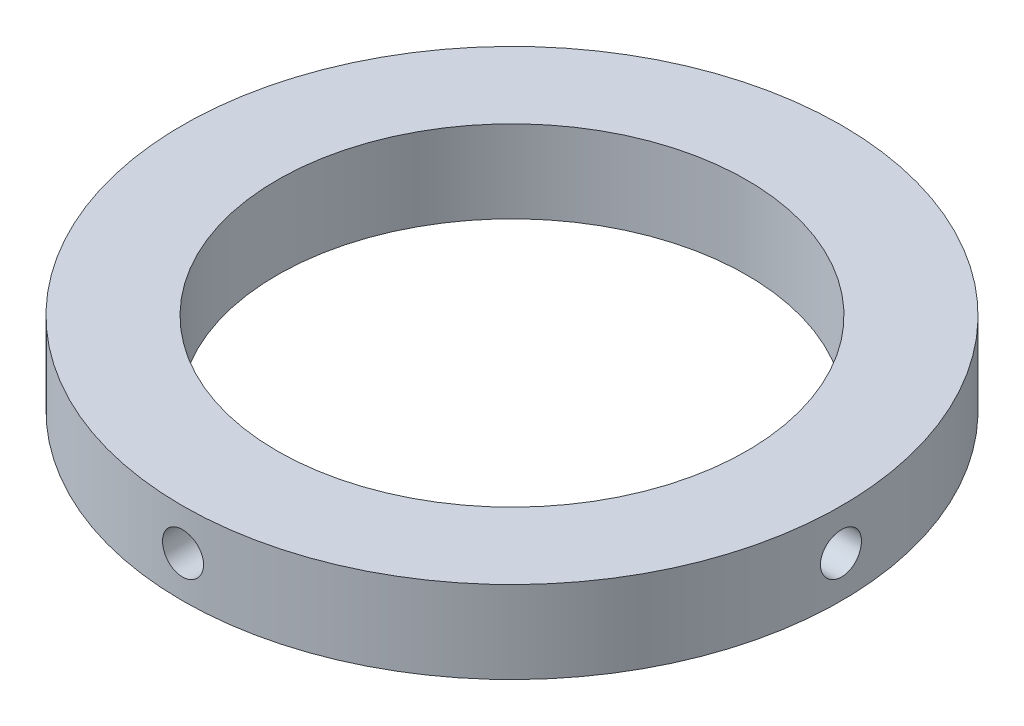
SolidWorks part; units mm, degrees
material "G10 Fiberglass"
ref_plane "Front Plane" through (0, 0, 0) normal (0, 0, 1) x (1, 0, 0)
ref_plane "Top Plane" through (0, 0, 0) normal (0, 1, 0) x (1, 0, 0)
ref_plane "Right Plane" through (0, 0, 0) normal (1, 0, 0) x (0, 0, -1)
sketch "Sketch1" plane through (0, 0, 0) normal (0, 0, 1) x (1, 0, 0)
  line L0 (0, 22.7096) -> (0, -29.6046) construction
  line L2 (27.178, -9.525) -> (38.1508, -9.525)
  line L3 (27.178, -9.525) -> (27.178, 0)
  line L4 (27.178, 0) -> (38.1508, 0)
  line L5 (38.1508, -9.525) -> (38.1508, 0)
  dimension "D1" = 76.3016
  dimension "D2" = 9.525
  dimension "D3" = 54.356
revolve "Revolve1" add sketch "Sketch1" angle 360 about L0
ref_plane "Plane1" through (-38.1508, 0, 0) normal (-1, 0, 0) x (0, 0, 1)
sketch "Sketch2" plane through (-38.1508, 0, 0) normal (-1, 0, 0) x (0, 0, 1)
  circle A0 centre (0, -4.7625) radius 2.3749
  point P2 (-6.7084, 0)
  point P4 (0, -5.6152)
  dimension "D2" = 4.7498
  dimension "D1" = 4.7625
extrude "Cut-Extrude1" cut sketch "Sketch2" against normal blind 6.35
ref_axis "Axis1" through (0, -10.0013, 0) along (0, 1, 0)
pattern_circular "CirPattern1" count 4 over 360 about axis through (0, -10.0013, 0) along (0, 1, 0) of "Cut-Extrude1"
